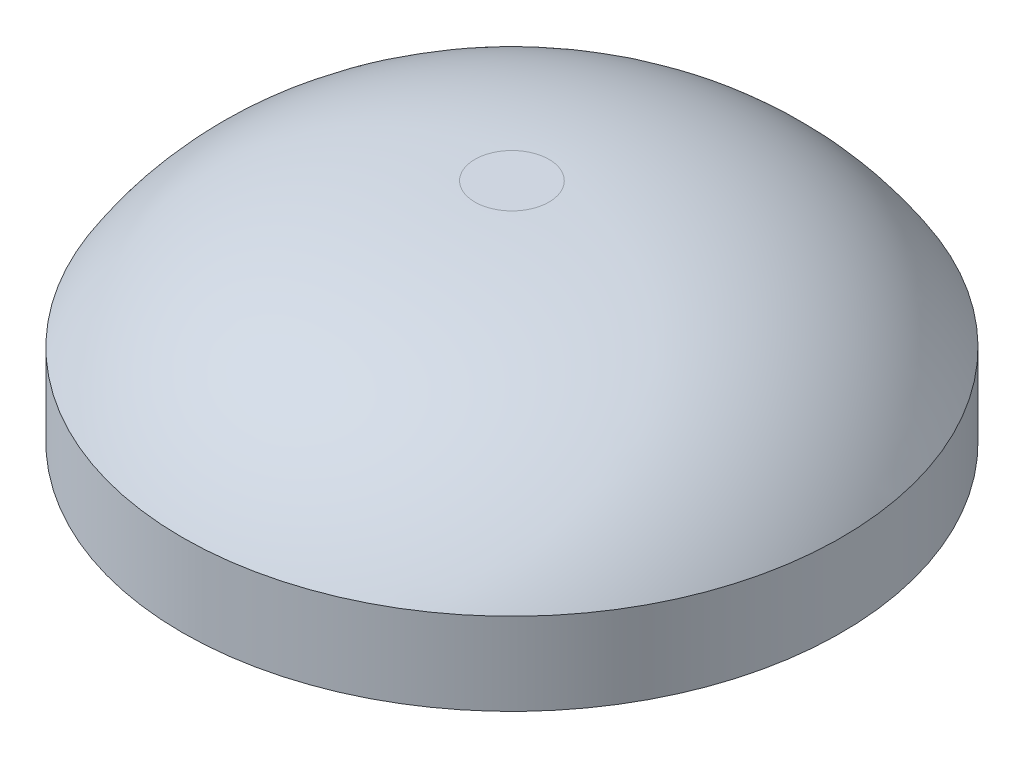
SolidWorks part; units mm, degrees
ref_plane "Plan de face" through (0, 0, 0) normal (0, 0, 1) x (1, 0, 0)
ref_plane "Plan de dessus" through (0, 0, 0) normal (0, 1, 0) x (1, 0, 0)
ref_plane "Plan de droite" through (0, 0, 0) normal (1, 0, 0) x (0, 0, -1)
sketch "Esquisse1" plane through (0, 0, 0) normal (0, 0, 1) x (1, 0, 0)
  line L0 (0, 1) -> (4, 1)
  line L1 (0, 0) -> (4, 0)
  line L2 (0, 0) -> (0, 2.75)
  line L3 (0, 2.75) -> (4, 2.75)
  line L4 (4, 0) -> (4, 2.75)
  spline S0 degree 2 poles (0, 2.75) (3.048, 2.8321) (4.1491, 0.7409) knots 0 0 0 1 1 1
  dimension "D1" = 4
  dimension "D2" = 2.75
  dimension "D3" = 1
ref_axis "Axe1" through (0, 2.75, 0) along (0, -1, 0)
revolve "Révolution1" add sketch "Esquisse1" angle 360 about axis through (0, 2.75, 0) along (0, -1, 0) region at (1.6144, 1.7448, 0) region at (2, 0.5, 0)
